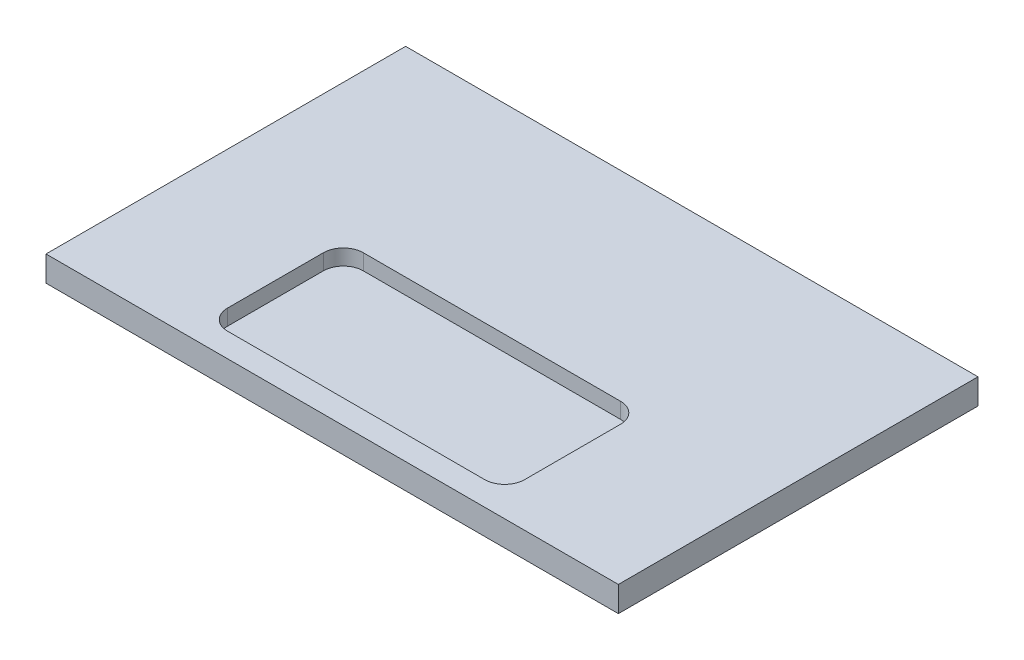
SolidWorks part; units mm, degrees
ref_plane "Front Plane" through (0, 0, 0) normal (0, 0, 1) x (1, 0, 0)
ref_plane "Top Plane" through (0, 0, 0) normal (0, 1, 0) x (1, 0, 0)
ref_plane "Right Plane" through (0, 0, 0) normal (1, 0, 0) x (0, 0, -1)
sketch "Sketch1" plane through (0, 0, 0) normal (0, 1, 0) x (1, 0, 0)
  line L0 (-192.1968, 11.8239) -> (94.8232, 11.8239)
  line L1 (94.8232, 11.8239) -> (94.8232, -168.5161)
  line L2 (94.8232, -168.5161) -> (-192.1968, -168.5161)
  line L3 (-192.1968, -168.5161) -> (-192.1968, 11.8239)
  dimension "D1" = 287.02
  dimension "D2" = 180.34
extrude "Boss-Extrude3" add sketch "Sketch1" along normal blind 12.7
sketch "Sketch3" plane through (0, 12.7, 0) normal (0, 1, 0) x (1, 0, 0)
  line L0 (-123.1868, -156.5161) -> (-123.1868, -88.4161)
  line L1 (-123.1868, -88.4161) -> (25.8132, -88.4161)
  line L2 (25.8132, -88.4161) -> (25.8132, -156.5161)
  line L3 (25.8132, -156.5161) -> (-123.1868, -156.5161)
  line L4 (-192.1968, -168.5161) -> (94.8232, -168.5161) construction
  dimension "D1" = 68.1
  dimension "D2" = 149
  dimension "D3" = 12
extrude "Cut-Extrude1" cut sketch "Sketch3" against normal blind 7.874
fillet "Fillet1" radius 10 4 edges at (25.8132, 8.763, 156.5161) (25.8132, 8.763, 88.4161) (-123.1868, 8.763, 156.5161) (-123.1868, 8.763, 88.4161)
sketch "Sketch5" plane through (0, 12.7, 0) normal (0, 1, 0) x (1, 0, 0)
  line L0 (-122.1868, -68.4161) -> (-122.1868, -57.0161)
  line L1 (-122.1868, -57.0161) -> (-110.1868, -57.0161)
  line L2 (-110.1868, -57.0161) -> (-110.1868, -68.4161)
  line L3 (-110.1868, -68.4161) -> (-122.1868, -68.4161)
  line L4 (-95.1868, -68.4161) -> (-107.1868, -68.4161)
  line L5 (-107.1868, -68.4161) -> (-107.1868, -57.0161)
  line L6 (-107.1868, -57.0161) -> (-95.1868, -57.0161)
  line L7 (-95.1868, -57.0161) -> (-95.1868, -68.4161)
  line L8 (-80.1868, -68.4161) -> (-92.1868, -68.4161)
  line L9 (-92.1868, -68.4161) -> (-92.1868, -57.0161)
  line L10 (-92.1868, -57.0161) -> (-80.1868, -57.0161)
  line L11 (-80.1868, -57.0161) -> (-80.1868, -68.4161)
  line L12 (-65.1868, -68.4161) -> (-77.1868, -68.4161)
  line L13 (-77.1868, -68.4161) -> (-77.1868, -57.0161)
  line L14 (-77.1868, -57.0161) -> (-65.1868, -57.0161)
  line L15 (-65.1868, -57.0161) -> (-65.1868, -68.4161)
  line L16 (-50.1868, -68.4161) -> (-62.1868, -68.4161)
  line L17 (-62.1868, -68.4161) -> (-62.1868, -57.0161)
  line L18 (-62.1868, -57.0161) -> (-50.1868, -57.0161)
  line L19 (-50.1868, -57.0161) -> (-50.1868, -68.4161)
  line L20 (-35.1868, -68.4161) -> (-47.1868, -68.4161)
  line L21 (-47.1868, -68.4161) -> (-47.1868, -57.0161)
  line L22 (-47.1868, -57.0161) -> (-35.1868, -57.0161)
  line L23 (-35.1868, -57.0161) -> (-35.1868, -68.4161)
  line L24 (-20.1868, -68.4161) -> (-32.1868, -68.4161)
  line L25 (-32.1868, -68.4161) -> (-32.1868, -57.0161)
  line L26 (-32.1868, -57.0161) -> (-20.1868, -57.0161)
  line L27 (-20.1868, -57.0161) -> (-20.1868, -68.4161)
  line L28 (-5.1868, -68.4161) -> (-17.1868, -68.4161)
  line L29 (-17.1868, -68.4161) -> (-17.1868, -57.0161)
  line L30 (-17.1868, -57.0161) -> (-5.1868, -57.0161)
  line L31 (-5.1868, -57.0161) -> (-5.1868, -68.4161)
  line L32 (9.8132, -68.4161) -> (-2.1868, -68.4161)
  line L33 (-2.1868, -68.4161) -> (-2.1868, -57.0161)
  line L34 (-2.1868, -57.0161) -> (9.8132, -57.0161)
  line L35 (9.8132, -57.0161) -> (9.8132, -68.4161)
  line L36 (24.8132, -68.4161) -> (12.8132, -68.4161)
  line L37 (12.8132, -68.4161) -> (12.8132, -57.0161)
  line L38 (12.8132, -57.0161) -> (24.8132, -57.0161)
  line L39 (24.8132, -57.0161) -> (24.8132, -68.4161)
  line L40 (-110.1868, -68.4161) -> (-95.1868, -68.4161) construction
  line L41 (-122.1868, -62.7161) -> (-192.1968, -62.7161)
  line L42 (-192.1968, 11.8239) -> (-192.1968, -168.5161) construction
  line L43 (24.8132, -62.7161) -> (94.8232, -62.7161)
  line L44 (94.8232, -168.5161) -> (94.8232, 11.8239) construction
  line L45 (15.8132, -88.4161) -> (-113.1868, -88.4161) construction
  line L47 (-53.5447, -85.6434) -> (-53.5447, -74.7707)
  line L48 (-53.5447, -74.7707) -> (-3.6418, -74.7707)
  line L49 (-3.6418, -74.7707) -> (-3.6418, -85.6434)
  line L50 (-3.6418, -85.6434) -> (-53.5447, -85.6434)
  point P45 (-122.1868, -62.7161)
  dimension "D1" = 12
  dimension "D2" = 11.4
  dimension "D4" = 15
  dimension "D5" = 20
  dimension "D3" = 10
